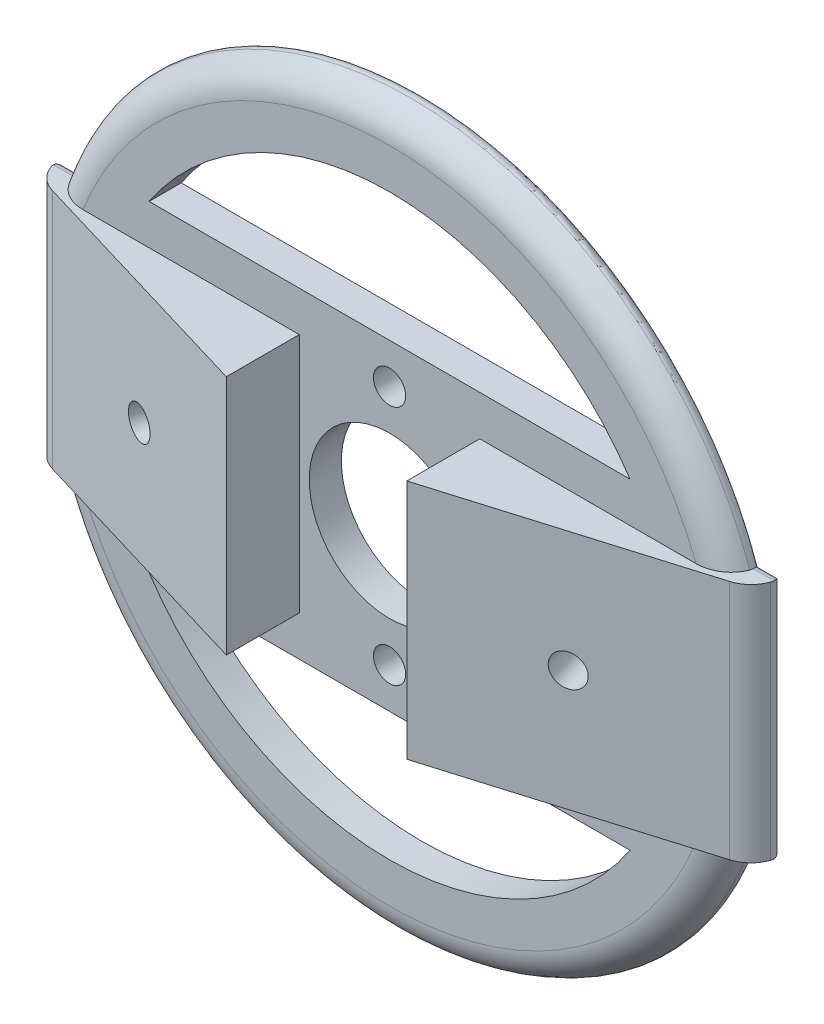
SolidWorks part; units mm, degrees
ref_plane "前视基准面" through (0, 0, 0) normal (0, 0, 1) x (1, 0, 0)
ref_plane "上视基准面" through (0, 0, 0) normal (0, 1, 0) x (1, 0, 0)
ref_plane "右视基准面" through (0, 0, 0) normal (1, 0, 0) x (0, 0, -1)
sketch "草图1" plane through (0, 0, 0) normal (0, 0, 1) x (1, 0, 0)
  circle A0 centre (0, 0) radius 45
  dimension "D1" = 90
extrude "凸台-拉伸1" add sketch "草图1" along normal blind 4
fillet "圆角1" radius 4 1 edges at (45, 0, 4)
sketch "草图2" plane through (0, 0, 4) normal (0, 0, 1) x (1, 0, 0)
  circle A0 centre (0, -15) radius 2 construction
  circle A1 centre (0, 15) radius 2 construction
  circle A2 centre (0, -15) radius 2
  circle A3 centre (0, 15) radius 2
extrude "切除-拉伸1" cut sketch "草图2" against normal blind 4
sketch "草图3" plane through (0, 0, 4) normal (0, 0, 1) x (1, 0, 0)
  line L0 (0, -41) -> (0, 41) construction
  circle A0 centre (0, 0) radius 41 construction
  circle A1 centre (27.5539, 0) radius 15
  circle A2 centre (-27.5539, 0) radius 15
sketch "草图4" plane through (0, 0, 0) normal (0, 1, 0) x (1, 0, 0)
  line L0 (42.1468, -3.8321) -> (11.2331, -13.0835)
  line L1 (45, 0) -> (11.2331, 0)
  line L2 (11.2331, -13.0835) -> (11.2331, -4)
  line L3 (-41, -4) -> (41, -4) construction
  line L4 (45, 0) -> (-45, 0) construction
  line L5 (11.2331, 0) -> (11.2331, -4)
  arc A0 (41, -4) -> (45, 0) centre (41, 0) ccw construction
  arc A1 (42.1468, -3.8321) -> (45, 0) centre (41, 0) ccw
extrude "凸台-拉伸2" add sketch "草图4" along normal mid plane 30
sketch "草图5" plane through (4.5169, 0, 15.0934) normal (0.2867, 0, 0.958) x (0.958, 0, -0.2867)
  circle A0 centre (23.1447, 0) radius 15 construction
  circle A1 centre (23.1447, 0) radius 2
  dimension "D1" = 4
extrude "切除-拉伸2" cut sketch "草图5" against normal blind 30
mirror "镜向1" [suppressed] about plane through (0, 0, 0) normal (1, 0, 0)
sketch "草图7" plane through (0, 0, 0) normal (0, 1, 0) x (1, 0, 0)
  line L0 (11.2331, -4) -> (11.2331, -23.3602)
  line L1 (45, 0) -> (45, -15.2037)
  line L3 (-41, -4) -> (38.1576, -4) construction
  line L4 (42.4264, 0) -> (45, 0)
  line L5 (0, 6.8473) -> (0, -30.9719) construction
  line L6 (-41, -4) -> (38.1576, -4)
  arc A0 (11.2331, -23.3602) -> (45, -15.2037) centre (0, 97.1173) ccw
  spline S0 degree 3 poles (-211.8223, -967.1343) (-1.4392, 38.7255) (44.7416, 10.1744) (42.2812, -1.0719) (42.196, -1.3278) (41.9705, -1.8234) (41.8321, -2.0581) (41.5125, -2.4928) (41.3284, -2.6963) (40.9267, -3.0605) (40.7101, -3.2212) (40.2468, -3.5015) (39.9993, -3.6206) (39.4939, -3.8094) (39.2335, -3.8805) (22.0901, -6.9474) (-6.0882, 86.5788) (1033.6221, 91.0464) knots -5.07479 -5.07479 -5.07479 -5.07479 0.125 0.125 0.25 0.25 0.375 0.375 0.5 0.5 0.625 0.625 0.75 0.75 0.875 0.875 8.74794 8.74794 8.74794 8.74794 only from (42.4264, 0) to (38.1576, -4) construction
  spline S1 degree 3 poles (42.4264, 0) (42.4264, -0.2697) (42.3967, -0.5439) (42.2812, -1.0719) (42.196, -1.3278) (41.9705, -1.8234) (41.8321, -2.0581) (41.5125, -2.4928) (41.3284, -2.6963) (40.9267, -3.0605) (40.7101, -3.2212) (40.2468, -3.5015) (39.9993, -3.6206) (39.4939, -3.8094) (39.2335, -3.8805) (38.6977, -3.9764) (38.4269, -4) (38.1576, -4) knots 0 0 0 0 0.125 0.125 0.25 0.25 0.375 0.375 0.5 0.5 0.625 0.625 0.75 0.75 0.875 0.875 1 1 1 1
revolve "旋转1" [suppressed] add sketch "草图7" angle 180 about L5
sketch "草图8" plane through (4.5169, 0, 15.0934) normal (0.2867, 0, 0.958) x (0.958, 0, -0.2867)
  circle A0 centre (23.1447, 0) radius 12.5
extrude "切除-拉伸4" [suppressed] cut sketch "草图8" along normal up to surface (11.9532 mm away)
mirror "镜向2" [suppressed] about plane through (0, 0, 0) normal (1, 0, 0)
sketch "草图10" [suppressed] plane through (4.5169, 0, 15.0934) normal (0.2867, 0, 0.958) x (0.958, 0, -0.2867)
  line L0 (21.1447, 0) -> (25.1447, 0) construction
  circle A0 centre (23.1447, 0) radius 2
extrude "切除-拉伸5" [suppressed] cut sketch "草图10" against normal blind 10
mirror "镜向3" [suppressed] about plane through (0, 0, 0) normal (1, 0, 0)
sketch "草图11" plane through (0, 0, 4) normal (0, 0, 1) x (1, 0, 0)
  circle A0 centre (0, 15) radius 5
extrude "切除-拉伸6" [suppressed] cut sketch "草图11" along normal blind 39
mirror "镜向6" [suppressed] of bodies 106 111
fillet "圆角2" [suppressed] radius 4
mirror "镜向7" about plane through (0, 0, 0) normal (1, 0, 0) of "切除-拉伸2", "凸台-拉伸2"
sketch "草图12" plane through (0, 0, 4) normal (0, 0, 1) x (1, 0, 0)
  line L6 (-6.2331, 20) -> (6.2331, 20)
  line L7 (-6.2331, -20) -> (6.2331, -20)
  line L12 (-29.9333, 20) -> (-6.2331, 20)
  line L13 (-6.2331, 20) -> (-6.2331, -20)
  line L14 (-6.2331, -20) -> (-29.9333, -20)
  line L15 (29.9333, -20) -> (6.2331, -20)
  line L16 (6.2331, -20) -> (6.2331, 20)
  line L17 (6.2331, 20) -> (29.9333, 20)
  line L18 (-29.9333, 20) -> (-6.2331, 20)
  line L20 (-6.2331, -20) -> (-29.9333, -20)
  line L21 (29.9333, -20) -> (6.2331, -20)
  line L23 (6.2331, 20) -> (29.9333, 20)
  circle A2 centre (0, 0) radius 10
  arc A4 (-29.9333, -20) -> (29.9333, -20) centre (0, 0) ccw
  arc A5 (29.9333, 20) -> (-29.9333, 20) centre (0, 0) ccw
  arc A6 (-29.9333, -20) -> (29.9333, -20) centre (0, 0) ccw
  arc A7 (29.9333, 20) -> (-29.9333, 20) centre (0, 0) ccw
  dimension "D2" = 20
  dimension "D1" = 5
extrude "切除-拉伸7" cut sketch "草图12" against normal blind 10
fillet "圆角3" radius 1 8 edges at (0, -45, 0) (0, 45, 0) (-43.7132, 15, 0) (-45, 0, 0) (-43.7132, -15, 0) (43.7132, -15, 0) (45, 0, 0) (43.7132, 15, 0)
